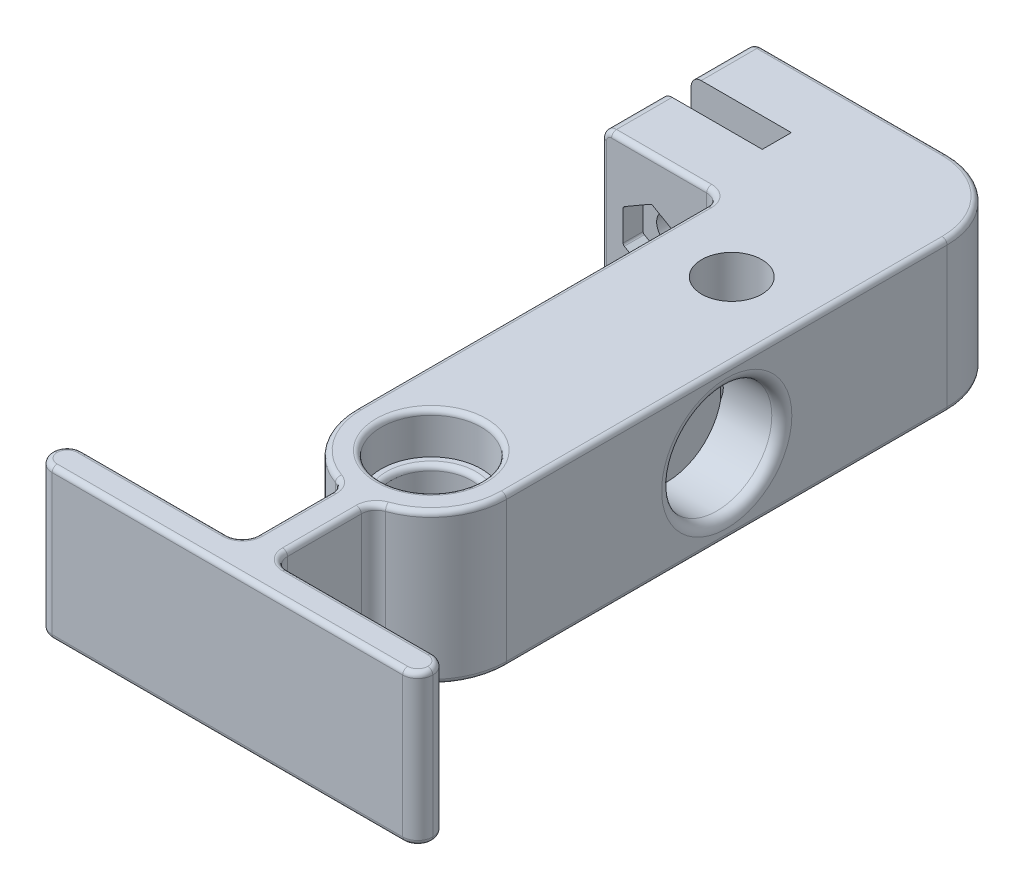
SolidWorks part; units mm, degrees
ref_plane "Front Plane" through (0, 0, 0) normal (0, 0, 1) x (1, 0, 0)
ref_plane "Top Plane" through (0, 0, 0) normal (0, 1, 0) x (1, 0, 0)
ref_plane "Right Plane" through (0, 0, 0) normal (1, 0, 0) x (0, 0, -1)
sketch "Sketch1" plane through (0, 0, 0) normal (0, 1, 0) x (1, 0, 0)
  line L0 (0, 22) -> (0, -22) construction
  line L1 (-7.5, 22) -> (7.5, 22)
  line L2 (-7.5, 22) -> (-7.5, -22)
  line L3 (-7.5, -22) -> (7.5, -22)
  line L4 (7.5, 22) -> (7.5, -22)
  line L5 (-7.5, 22) -> (7.5, -22) construction
  line L6 (-7.5, -22) -> (7.5, 22) construction
  circle A0 centre (0, -14.5) radius 4
  circle A1 centre (0, -14.5) radius 7.5
  point P0 (0, 0)
  dimension "D1" = 8
  dimension "D2" = 15
  dimension "D4" = 44
extrude "Boss-Extrude1" add sketch "Sketch1" along normal mid plane 15 contours L2 | L4 | A1 L4 L1 L2 | A1 A0 | L3 region at (0, 0, -6.6495) region at (0, 0, 7.2121)
sketch "Sketch2" plane through (0, 7.5, 0) normal (0, 1, 0) x (1, 0, 0)
  circle A0 centre (0, -14.5) radius 5
  dimension "D1" = 10
extrude "Cut-Extrude1" cut sketch "Sketch2" against normal blind 4.1
mirror "Mirror1" about plane through (0, 0, 0) normal (0, 1, 0) of "Cut-Extrude1"
sketch "Sketch12" plane through (0, -3.4, 0) normal (0, -1, 0) x (1, 0, 0)
  circle A0 centre (0, 14.5) radius 4 construction
  circle A1 centre (0, 14.5) radius 5
  circle A2 centre (0, 14.5) radius 5
  circle A3 centre (0, 14.5) radius 4
  dimension "D1" = 0
extrude "Cut-Extrude10" cut sketch "Sketch12" against normal blind 0.5
sketch "Sketch4" plane through (7.5, 0, 0) normal (1, 0, 0) x (0, 0, -1)
  line L0 (-3.1918, 0) -> (3.917, 0) construction
  line L2 (-9.5, 7.5) -> (-19.5, 7.5) construction
  line L3 (-9.5, 7.5) -> (-19.5, 7.5)
  line L4 (-14.5, 7.5) -> (-14.5, -7.5) construction
  line L5 (22, -7.5) -> (-14.5, -7.5) construction
  line L6 (7.5, 0) -> (7.5, 7.5) construction
  line L9 (22, 7.5) -> (-14.5, 7.5) construction
  circle A1 centre (7.5, 0) radius 5.5
  dimension "D1" = 22
  dimension "D2" = 11
extrude "Cut-Extrude3" cut sketch "Sketch4" against normal blind 6 contours A1 region at (7.5, 0, -7.5)
mirror "Mirror2" about plane through (0, 0, 0) normal (1, 0, 0) of "Cut-Extrude3"
sketch "Sketch18" plane through (0, -7.5, 0) normal (0, -1, 0) x (1, 0, 0)
  line L0 (0, -41.3409) -> (0, 22.3101) construction
  line L4 (7.5, -3.75) -> (-7.5, -3.75) construction
  line L5 (-19.5, -22) -> (-7.5, -22)
  line L6 (7.5, -29.5) -> (7.5, -22)
  line L7 (7.5, -22) -> (7.5, 14.5) construction
  line L8 (-7.5, -22) -> (7.5, -22)
  line L9 (-7.5, -22) -> (-7.5, 14.5) construction
  line L10 (0, -22) -> (0, -37) construction
  line L11 (0, -37) -> (-19.5, -37)
  line L13 (-19.5, -22) -> (-19.5, -37)
  circle A1 centre (0, -29.5) radius 7.5
  line M10 (-7.5, -22) -> (7.5, -22)
  dimension "D1" = 12
extrude "Boss-Extrude3" add sketch "Sketch18" against normal up to surface (15 mm away) contours A1 L6 L8 | A1 M10 | A1 | A1 L13 L11 region at (-12.5923, -7.5, -29.5) region at (5.8247, -7.5, -23.6753) region at (0, -7.5, -29.5) up to face at (0, 7.5, 19.5)
sketch "Sketch7" plane through (0, 7.5, 0) normal (0, 1, 0) x (1, 0, 0)
  line L0 (-19.5, 29.5) -> (7.5, 29.5) construction
  line L8 (7.5, 29.5) -> (7.5, -14.5) construction
  line L9 (-19.5, 28.05) -> (-9.5, 28.05)
  line L10 (-19.5, 28.05) -> (-19.5, 30.95)
  line L11 (-9.5, 28.05) -> (-9.5, 30.95)
  line L12 (-19.5, 30.95) -> (-9.5, 30.95)
  line L13 (-19.5, 28.05) -> (-9.5, 30.95) construction
  line L14 (-9.5, 28.05) -> (-19.5, 30.95) construction
  line L15 (-19.5, 22) -> (-19.5, 37) construction
  point P8 (-14.5, 29.5)
  dimension "D1" = 10
  dimension "D2" = 2.9
extrude "Cut-Extrude7" cut sketch "Sketch7" against normal up to next
sketch "Sketch8" plane through (-40.2452, 0, -37) normal (0, 0, 1) x (1, 0, 0)
  line L5 (20.7452, 0) -> (40.2452, 0) construction
  line L8 (20.7452, 7.5) -> (20.7452, -7.5) construction
  line L9 (40.2452, 7.5) -> (40.2452, -7.5) construction
  circle A2 centre (25.7452, 0) radius 1.5
  dimension "D2" = 5
  dimension "D3" = 3
extrude "Cut-Extrude8" cut sketch "Sketch8" along normal up to surface (15 mm away) contours A2
hole_wizard "CSK for M3 Flat Head Machine Screw1" positions "Sketch9" profile "Sketch10" countersink size "M3" standard "ANSI Metric"
sketch "Sketch9" plane through (-83.1458, 0, -37) normal (0, 0, 1) x (1, 0, 0)
  point P6 (68.6458, 0)
  point P17 (0, 0)
  point P18 (0, 0)
  point P19 (0, 0)
  point P20 (0, 0)
sketch "Sketch10" plane through (-14.5, 0, -37) normal (1, 0, 0) x (0, 1, 0)
  line L0 (0, 0) -> (0, 5.9013)
  line L1 (0, 5.9013) -> (1.5, 5)
  line L2 (1.5, 5) -> (1.5, 1.8)
  line L3 (1.5, 1.8) -> (3, 0.3)
  line L4 (3, 0.3) -> (3, 0)
  line L6 (3, 0) -> (0, 0)
  line L7 (-1.5, 1.8) -> (-3, 0.3) construction
  line L10 (0, 5.9013) -> (-1.5, 5) construction
  line L11 (0, -6.35) -> (0, 107.95) construction
  dimension "Hole Dia." = 3
  dimension "Hole Depth" = 5
  dimension "C'Sink Dia." = 6
  dimension "C'Sink Angle" = 90
  dimension "Drill Angle" = 118
  dimension "Head Clearance" = 0.3
sketch "Sketch11" plane through (15, 0, -22) normal (0, 0, 1) x (1, 0, 0)
  line L7 (-34.5, 7.5) -> (-34.5, -7.5) construction
  line L8 (-29.5, -3.2909) -> (-26.65, -1.6454)
  line L15 (-26.65, -1.6454) -> (-26.65, 1.6454)
  line L16 (-26.65, 1.6454) -> (-29.5, 3.2909)
  line L17 (-29.5, 3.2909) -> (-32.35, 1.6454)
  line L18 (-32.35, 1.6454) -> (-32.35, -1.6454)
  line L19 (-32.35, -1.6454) -> (-29.5, -3.2909)
  circle A0 centre (-29.5, 0) radius 2.85 construction
  dimension "D1" = 5.7
extrude "Cut-Extrude9" cut sketch "Sketch11" against normal blind 2
sketch "Sketch13" plane through (-44.6536, 0, -30.95) normal (0, 0, 1) x (1, 0, 0)
  line L0 (35.1536, -7.5) -> (35.1536, 7.5) construction
  line L2 (35.1536, -7.5) -> (35.1536, 7.5)
  line L3 (35.1536, 0) -> (44.6536, 0) construction
  line L4 (44.6536, 7.5) -> (44.6536, -7.5) construction
  line L5 (35.1536, 7.5) -> (42.6536, 0)
  line L6 (35.1536, -7.5) -> (42.6536, 0)
  dimension "D1" = 45
extrude "Cut-Extrude11" cut sketch "Sketch13" along normal up to surface (2.9 mm away) contours L5 L6 L2 up to face at (-13, 0, -28.05)
sketch "Sketch16" plane through (0, -7.5, 0) normal (0, -1, 0) x (1, 0, 0)
  line L0 (0, 42.718) -> (0, -5.4521) construction
  line L2 (-1.5, 31.8485) -> (1.5, 31.8485)
  line L3 (-1.5, 31.8485) -> (-1.5, 21.8485)
  line L4 (-1.5, 21.8485) -> (1.5, 21.8485)
  line L5 (1.5, 31.8485) -> (1.5, 21.8485)
  line L6 (-1.5, 31.8485) -> (1.5, 21.8485) construction
  line L7 (-1.5, 21.8485) -> (1.5, 31.8485) construction
  line L8 (-19, 34.8485) -> (19, 34.8485)
  line L9 (-19, 34.8485) -> (-19, 31.8485)
  line L10 (-19, 31.8485) -> (19, 31.8485)
  line L11 (19, 34.8485) -> (19, 31.8485)
  line L12 (-19, 34.8485) -> (19, 31.8485) construction
  line L13 (-19, 31.8485) -> (19, 34.8485) construction
  arc A0 (7.5, 14.5) -> (-7.5, 14.5) centre (0, 14.5) ccw construction
  point P1 (0, 26.8485)
  point P11 (0, 33.3485)
  arc M14 (7.5, 14.5) -> (-7.5, 14.5) centre (0, 14.5) ccw
  dimension "D1" = 3
  dimension "D2" = 10
  dimension "D3" = 38
extrude "Boss-Extrude2" add sketch "Sketch16" against normal up to surface (15 mm away) contours L5 L2 L3 M14 | L11 L8 L9 L10 L2 region at (0, -7.5, 33.3485) region at (0, -7.5, 26.899) up to face at (-8.677, 7.5, -20.9594)
sketch "Sketch19" plane through (0, -7.5, 0) normal (0, -1, 0) x (1, 0, 0)
  line L0 (0, 4.3088) -> (0, -5.4508) construction
  circle A0 centre (0, -15.5) radius 3
  circle A2 centre (0, 14.5) radius 5 construction
  dimension "D1" = 6
  dimension "D2" = 30
extrude "Cut-Extrude12" cut sketch "Sketch19" against normal up to next contours A0
fillet "Fillet12" radius 1.5 9 edges at (-1.5, 0, 31.8485) (-19, 0, 34.8485) (-19, 0, 31.8485) (-1.5, 0, 21.8485) (1.5, 0, 21.8485) (1.5, 0, 31.8485) (19, 0, 34.8485) (19, 0, 31.8485) (-7.5, 0, -22)
fillet "Fillet9" radius 1 6 edges at (-7.5, 0, -13) (7.5, 0, -13) (-19.5, 7.5, -25.025) (-19.5, -7.5, -25.025) (-19.5, -7.5, -33.975) (-19.5, 7.5, -33.975)
fillet "Fillet11" radius 0.25 6 edges at (-17.35, 1.6454, -23) (-17.35, -1.6454, -23) (-14.5, -3.2909, -23) (-11.65, -1.6454, -23) (-11.65, 1.6454, -23) (-14.5, 3.2909, -23)
fillet "Fillet10" radius 0.5 49 edges at (-7.5, -7.5, -3) (-6.1237, -7.5, 18.8301) (-1.5, -7.5, 26.6669) (0, -7.5, 34.8485) (1.5, -7.5, 26.6669) (6.1237, -7.5, 18.8301) (7.5, -7.5, -7.5) (5.3033, -7.5, -34.8033) (-9.25, -7.5, -37) (-19.5, 0, -37) (-9.25, 7.5, -37) (5.3033, 7.5, -34.8033) (7.5, 7.5, -7.5) (6.1237, 7.5, 18.8301) (1.5, 7.5, 26.6669) (0, 7.5, 34.8485) (-1.5, 7.5, 26.6669) (-6.1237, 7.5, 18.8301) (-7.5, 7.5, -3) (0, -7.5, 19.5) (0, 7.5, 19.5) (0, -2.9, 10.5) (0, 3.4, 18.5) (-1.7753, -7.5, 22.1193) (-1.9393, -7.5, 31.4091) (-10.25, -7.5, 31.8485) (-18.5607, -7.5, 32.2878) (-18.5607, -7.5, 34.4091) (18.5607, -7.5, 34.4091) (18.5607, -7.5, 32.2878) (10.25, -7.5, 31.8485) (1.9393, -7.5, 31.4091) (1.7753, -7.5, 22.1193) (-19.2071, -7.2071, -37) (-19.2071, 7.2071, -37) (1.7753, 7.5, 22.1193) (1.9393, 7.5, 31.4091) (10.25, 7.5, 31.8485) (18.5607, 7.5, 32.2878) (18.5607, 7.5, 34.4091) (-18.5607, 7.5, 34.4091) (-18.5607, 7.5, 32.2878) (-10.25, 7.5, 31.8485) (-1.9393, 7.5, 31.4091) (-1.7753, 7.5, 22.1193) (-7.9393, 7.5, -21.5607) (-13.75, 7.5, -22) (-19.2071, 7.2071, -22) (-7.9393, -7.5, -21.5607)
